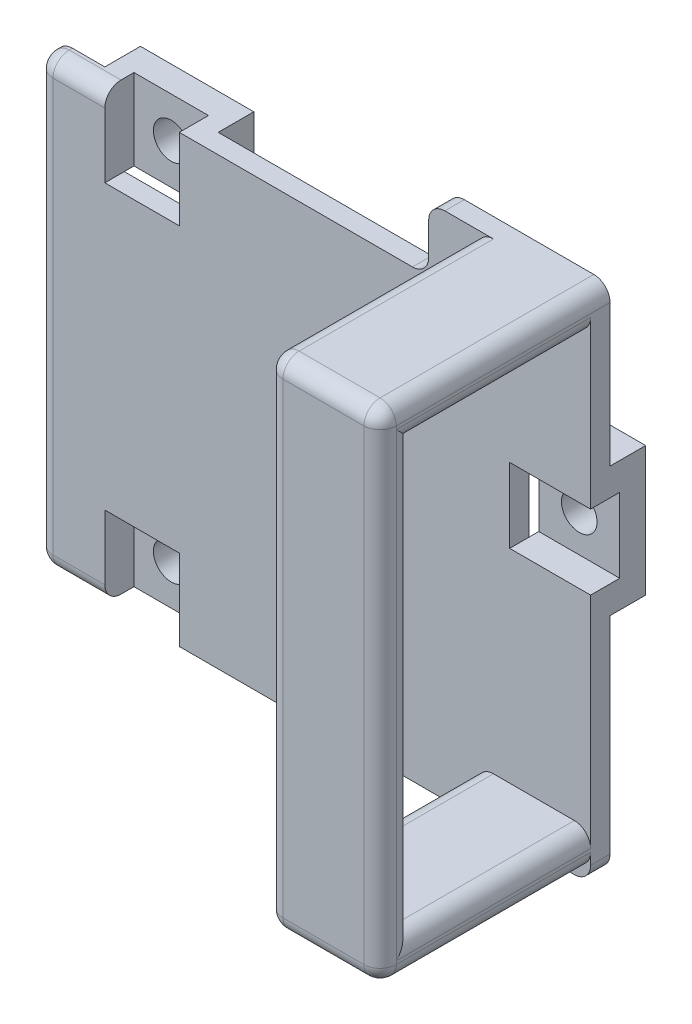
SolidWorks part; units mm, degrees
ref_plane "Płaszczyzna przednia" through (0, 0, 0) normal (0, 0, 1) x (1, 0, 0)
ref_plane "Płaszczyzna górna" through (0, 0, 0) normal (0, 1, 0) x (1, 0, 0)
ref_plane "Płaszczyzna prawa" through (0, 0, 0) normal (1, 0, 0) x (0, 0, -1)
sketch "Szkic1" plane through (0, 0, 158.8329) normal (0, 0, 1) x (1, 0, 0)
  line L0 (-31.9233, -22.4743) -> (2.0767, -22.4743) construction
  line L1 (-17.2684, -17.4743) -> (-10.2684, -17.4743)
  line L2 (-17.2684, -17.4743) -> (-17.2684, -22.4743)
  line L3 (-17.2684, -22.4743) -> (-10.2684, -22.4743)
  line L4 (-10.2684, -17.4743) -> (-10.2684, -22.4743)
  line L5 (-17.2684, -17.4743) -> (-10.2684, -22.4743) construction
  line L6 (-17.2684, -22.4743) -> (-10.2684, -17.4743) construction
  line L12 (13.9316, -0.7243) -> (8.9316, -0.7243)
  line L13 (13.9316, -0.7243) -> (13.9316, -8.7243)
  line L14 (-17.2684, 0.0257) -> (-10.2684, 0.0257)
  line L15 (-17.2684, 0.0257) -> (-17.2684, 5.0257)
  line L16 (-17.2684, 5.0257) -> (-10.2684, 5.0257)
  line L17 (-10.2684, 0.0257) -> (-10.2684, 5.0257)
  line L18 (-17.2684, 0.0257) -> (-10.2684, 5.0257) construction
  line L19 (-17.2684, 5.0257) -> (-10.2684, 0.0257) construction
  line L20 (13.9316, -8.7243) -> (8.9316, -8.7243)
  line L21 (8.9316, -0.7243) -> (8.9316, -8.7243)
  circle A3 centre (11.4316, -4.7243) radius 1.1
  circle A4 centre (-13.7684, -19.9743) radius 1.1
  circle A5 centre (-13.7684, 2.5257) radius 1.1
  point P1 (0, 0)
  point P3 (-18.3823, 5.0257)
  point P5 (6.2549, -0.7243)
  point P23 (-17.2684, 5.0257)
  point P24 (0, 0)
  dimension "D4" = 2.2
  dimension "D13" = 2.2
  dimension "D14" = 2.2
  dimension "D1" = 22.5
  dimension "D2" = 25.2
  dimension "D3" = 2.5
  dimension "D5" = 25.2
  dimension "D6" = 15.25
  dimension "D7" = 2.5
  dimension "D8" = 3.5
  dimension "D9" = 2.5
  dimension "D10" = 2.5
  dimension "D11" = 4
  dimension "D12" = 4
  dimension "D15" = 3.5
extrude "Dodanie-wyciągnięcie1" add sketch "Szkic1" along normal blind 2.2
sketch "Szkic2" plane through (0, 0, 161.0329) normal (0, 0, 1) x (1, 0, 0)
  line L11 (-20.2684, 5.0257) -> (13.9316, 5.0257)
  line L18 (13.9316, -22.4743) -> (-20.2684, -22.4743)
  line L20 (-10.2684, 5.0257) -> (-17.2684, 5.0257) construction
  line L21 (-20.2684, 5.0257) -> (-20.2684, -22.4743)
  line L22 (-17.2684, 5.0257) -> (-17.2684, 0.0257) construction
  line L23 (13.9316, 5.0257) -> (13.9316, -22.4743)
  line L24 (13.9316, -8.7243) -> (13.9316, -0.7243) construction
  line L25 (-17.2684, -22.4743) -> (-10.2684, -22.4743) construction
  circle A9 centre (11.4316, -4.7243) radius 1.1
  circle A10 centre (-13.7684, -19.9743) radius 1.1
  circle A11 centre (-13.7684, 2.5257) radius 1.1
  dimension "D1" = 3
extrude "Dodanie-wyciągnięcie2" add sketch "Szkic2" along normal blind 1.2
sketch "Szkic7" plane through (0, 5.0257, 0) normal (0, 1, 0) x (1, 0, 0)
  line L1 (13.9316, -162.2329) -> (3.9316, -162.2329)
  line L2 (13.9316, -162.2329) -> (13.9316, -161.0329)
  line L3 (13.9316, -161.0329) -> (3.9316, -161.0329)
  line L4 (3.9316, -162.2329) -> (3.9316, -161.0329)
  line L5 (13.9316, -161.0329) -> (-10.2684, -161.0329) construction
  point P5 (3.9318, -160.6329)
  point P8 (13.9316, -160.6329)
  dimension "D1" = 10
  dimension "D2" = 1.2
extrude "Dodanie-wyciągnięcie3" add sketch "Szkic7" along normal blind 4
sketch "Sketch1" plane through (0, 0, 162.2329) normal (0, 0, 1) x (1, 0, 0)
  line L1 (6.9316, -21.7811) -> (13.9316, -21.7811)
  line L2 (6.9316, -21.7811) -> (6.9316, -19.5811)
  line L3 (6.9316, -19.5811) -> (13.9316, -19.5811)
  line L4 (13.9316, -21.7811) -> (13.9316, -19.5811)
  line L5 (3.9316, 9.0257) -> (13.9316, 9.0257) construction
  line L6 (6.9316, 9.0257) -> (13.9316, 9.0257)
  line L7 (6.9316, 9.0257) -> (6.9316, 6.8257)
  line L8 (6.9316, 6.8257) -> (13.9316, 6.8257)
  line L9 (13.9316, 9.0257) -> (13.9316, 6.8257)
  point P12 (13.9316, 9.0257)
  point P15 (13.9316, 9.0257)
  point P16 (12.1995, 9.0257)
  point P17 (13.9316, 9.0257)
  dimension "D1" = 7
  dimension "D3" = 2.2
  dimension "D4" = 2.2
extrude "Boss-Extrude2" add sketch "Sketch1" along normal blind 11
sketch "Sketch2" plane through (0, 0, 173.2329) normal (0, 0, 1) x (1, 0, 0)
  line L1 (6.9316, -21.7811) -> (13.9316, -21.7811)
  line L2 (6.9316, -21.7811) -> (6.9316, 9.0257)
  line L3 (6.9316, 9.0257) -> (13.9316, 9.0257)
  line L4 (13.9316, -21.7811) -> (13.9316, 9.0257)
  line L5 (6.9316, -21.7811) -> (13.9316, -21.7811) construction
extrude "Boss-Extrude3" add sketch "Sketch2" along normal blind 2
sketch "Sketch3" plane through (0, 0, 162.2329) normal (0, 0, 1) x (1, 0, 0)
  line L0 (-20.2684, -22.4743) -> (13.9316, -22.4743) construction
  line L1 (-16.0684, -22.4743) -> (-11.4684, -22.4743)
  line L2 (-16.0684, -22.4743) -> (-16.0684, -17.4743)
  line L3 (-16.0684, -17.4743) -> (-11.4684, -17.4743)
  line L4 (-11.4684, -22.4743) -> (-11.4684, -17.4743)
  line L5 (3.9316, 5.0257) -> (-20.2684, 5.0257) construction
  line L6 (-16.0684, 5.0257) -> (-11.4684, 5.0257)
  line L7 (-16.0684, 5.0257) -> (-16.0684, 0.0257)
  line L8 (-16.0684, 0.0257) -> (-11.4684, 0.0257)
  line L9 (-11.4684, 5.0257) -> (-11.4684, 0.0257)
  line L11 (8.9316, -7.0243) -> (13.9316, -7.0243)
  line L12 (8.9316, -7.0243) -> (8.9316, -2.4243)
  line L13 (8.9316, -2.4243) -> (13.9316, -2.4243)
  line L14 (13.9316, -7.0243) -> (13.9316, -2.4243)
  line L15 (13.9316, -21.7811) -> (13.9316, 9.0257) construction
  circle A0 centre (-13.7684, -19.9743) radius 1.1 construction
  circle A1 centre (-13.7684, 2.5257) radius 1.1 construction
  circle A2 centre (11.4316, -4.7243) radius 1.1 construction
  circle A3 centre (-13.7684, -19.9743) radius 1.1
  circle A4 centre (-13.7684, 2.5257) radius 1.1
  circle A5 centre (11.4316, -4.7243) radius 1.1
  dimension "D1" = 2.3
  dimension "D2" = 2.3
  dimension "D3" = 2.5
  dimension "D4" = 2.5
  dimension "D5" = 2.3
  dimension "D6" = 2.3
  dimension "D7" = 2.3
  dimension "D8" = 2.3
  dimension "D9" = 2.5
extrude "Cut-Extrude1" cut sketch "Sketch3" against normal blind 1.8
fillet "Fillet1" radius 1 2 edges at (13.9316, -6.3777, 173.2329) (6.9316, -6.3777, 173.2329)
fillet "Fillet2" radius 1 6 edges at (13.9316, -22.4743, 161.6329) (3.9316, 5.0257, 161.6329) (3.9316, 9.0257, 161.6329) (13.9316, 9.0257, 168.1329) (-20.2684, -22.4743, 161.6329) (-20.2684, 5.0257, 161.6329)
fillet "Fillet4" radius 1 3 edges at (6.9316, 6.8257, 168.2329) (6.9316, -19.5811, 168.2329) (6.9316, 9.0257, 168.7329)
fillet "Fillet7" radius 1 2 edges at (6.9316, -21.7811, 168.7329) (13.8833, -21.7811, 168.7329)
fillet "Fillet8" radius 1 2 edges at (13.9316, -19.5811, 168.2329) (13.9316, 6.8257, 168.2329)
fillet "Fillet9" radius 1 8 edges at (7.2245, 8.7329, 175.2329) (10.4316, 9.0257, 175.2329) (13.6387, 8.7329, 175.2329) (13.9316, -6.3777, 175.2329) (13.6387, -21.4883, 175.2329) (10.4316, -21.7811, 175.2329) (7.2245, -21.4883, 175.2329) (6.9316, -6.3777, 175.2329)
fillet "Fillet10" radius 1 5 edges at (-17.6684, 5.0257, 162.2329) (-19.9755, 4.7329, 162.2329) (-17.6684, -22.4743, 162.2329) (-19.9755, -22.1814, 162.2329) (-20.2684, -8.7243, 162.2329)
